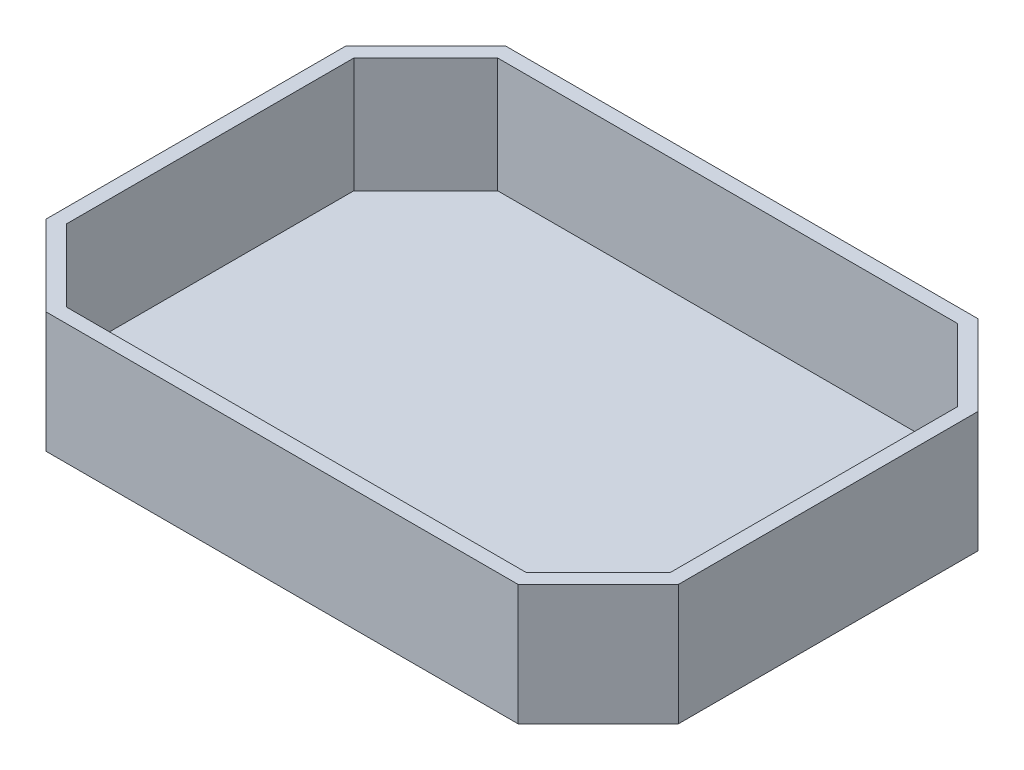
SolidWorks part; units mm, degrees
ref_plane "Front Plane" through (0, 0, 0) normal (0, 0, 1) x (1, 0, 0)
ref_plane "Top Plane" through (0, 0, 0) normal (0, 1, 0) x (1, 0, 0)
ref_plane "Right Plane" through (0, 0, 0) normal (1, 0, 0) x (0, 0, -1)
ref_axis "X" through (-88.99, 0, 0) along (1, 0, 0)
ref_axis "Y" through (0, 55, 0) along (0, -1, 0)
ref_axis "Z" through (0, 0, -88.99) along (0, 0, 1)
sketch "Sketch1" plane through (0, 0, 0) normal (0, 1, 0) x (1, 0, 0)
  line L0 (80, 75) -> (105, 50)
  line L1 (-80, 75) -> (80, 75)
  line L2 (-80, 75) -> (-80, -75) construction
  line L3 (-80, -75) -> (80, -75)
  line L4 (80, 75) -> (80, -75) construction
  line L5 (-80, 75) -> (80, -75) construction
  line L6 (-80, -75) -> (80, 75) construction
  line L7 (105, 50) -> (105, -50)
  line L8 (105, -50) -> (80, -75)
  line L9 (80, 0) -> (105, 0) construction
  line L10 (0, 0) -> (0, 75) construction
  line L11 (-105, -50) -> (-80, -75)
  line L12 (-105, 50) -> (-105, -50)
  line L13 (-80, 75) -> (-105, 50)
  line L14 (110, 52.0711) -> (110, -52.0711)
  line L15 (110, -52.0711) -> (82.0711, -80)
  line L16 (-82.0711, -80) -> (82.0711, -80)
  line L17 (-110, -52.0711) -> (-82.0711, -80)
  line L18 (-110, 52.0711) -> (-110, -52.0711)
  line L19 (-82.0711, 80) -> (-110, 52.0711)
  line L20 (-82.0711, 80) -> (82.0711, 80)
  line L21 (82.0711, 80) -> (110, 52.0711)
  point P0 (0, 0)
  dimension "D1" = 150
  dimension "D2" = 160
  dimension "D3" = 100
  dimension "D4" = 45
  dimension "D5" = 5
extrude "Boss-Extrude1" add sketch "Sketch1" against normal blind 2 contours L18 L17 L16 L15 L14 L21 L20 L19
extrude "Boss-Extrude2" add sketch "Sketch1<3>" along normal blind 40 contours L21 L20 L19 L18 L17 L16 L15 L14 L13 L1 L0 L7 L8 L3 L11 L12 region at (107.2797, 0, 0)
sketch "Sketch1<3>" plane through (0, 0, 0) normal (0, 1, 0) x (1, 0, 0) same geometry as "Sketch1"
